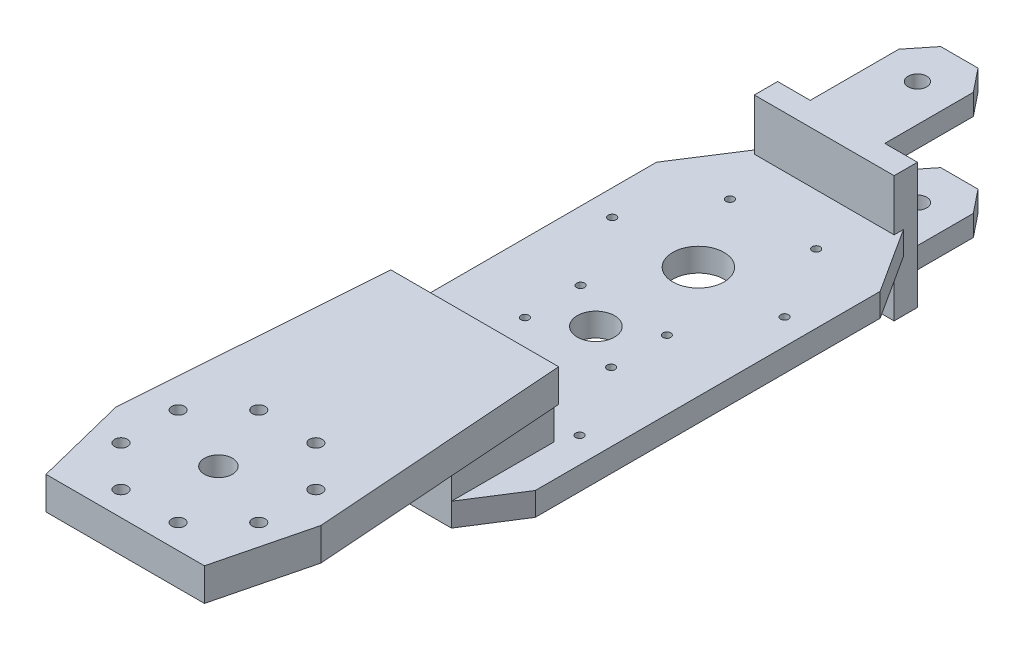
SolidWorks part; units mm, degrees
ref_plane "Front Plane" through (0, 0, 0) normal (0, 0, 1) x (1, 0, 0)
ref_plane "Top Plane" through (0, 0, 0) normal (0, 1, 0) x (1, 0, 0)
ref_plane "Right Plane" through (0, 0, 0) normal (1, 0, 0) x (0, 0, -1)
ref_plane "PL_Knee_Plate_base" through (0, 20, 0) normal (0, 1, 0) x (1, 0, 0)
sketch "SK_Knee_Plate" plane through (0, 20, 0) normal (0, 1, 0) x (1, 0, 0)
  line L0 (-34, -40) -> (34, -40)
  line L1 (34, -40) -> (44, 0)
  line L2 (44, 0) -> (36, 110)
  line L3 (36, 110) -> (-36, 110)
  line L4 (-36, 110) -> (-44, 0)
  line L5 (-44, 0) -> (-34, -40)
  circle A0 centre (29.5641, 12.2459) radius 2.75
  circle A1 centre (12.2459, 29.5641) radius 2.75
  circle A2 centre (-12.2459, 29.5641) radius 2.75
  circle A3 centre (-29.5641, 12.2459) radius 2.75
  circle A4 centre (-29.5641, -12.2459) radius 2.75
  circle A5 centre (-12.2459, -29.5641) radius 2.75
  circle A6 centre (12.2459, -29.5641) radius 2.75
  circle A7 centre (29.5641, -12.2459) radius 2.75
  circle A8 centre (0, 0) radius 6
  dimension "D11_SK_Knee_Plate" = 5.5
  dimension "D14_SK_Knee_Plate" = 5.5
  dimension "D17_SK_Knee_Plate" = 5.5
  dimension "D20_SK_Knee_Plate" = 5.5
  dimension "D23_SK_Knee_Plate" = 5.5
  dimension "D26_SK_Knee_Plate" = 5.5
  dimension "D29_SK_Knee_Plate" = 5.5
  dimension "D32_SK_Knee_Plate" = 5.5
  dimension "D35_SK_Knee_Plate" = 12
  dimension "P1" = 34
  dimension "P2" = 40
  dimension "P3" = 34
  dimension "P4" = 40
  dimension "P5" = 44
  dimension "P6" = 36
  dimension "P7" = 110
  dimension "P8" = 36
  dimension "P9" = 110
  dimension "P10" = 44
  dimension "P12" = 29.5641
  dimension "P13" = 12.2459
  dimension "P15" = 12.2459
  dimension "P16" = 29.5641
  dimension "P18" = 12.2459
  dimension "P19" = 29.5641
  dimension "P21" = 29.5641
  dimension "P22" = 12.2459
  dimension "P24" = 29.5641
  dimension "P25" = 12.2459
  dimension "P27" = 12.2459
  dimension "P28" = 29.5641
  dimension "P30" = 12.2459
  dimension "P31" = 29.5641
  dimension "P33" = 29.5641
  dimension "P34" = 12.2459
extrude "Knee_Plate" add sketch "SK_Knee_Plate" along normal blind 14
ref_plane "PL_Knee_Pilot_Recess_base" through (0, 20, 0) normal (0, 1, 0) x (1, 0, 0)
sketch "SK_Knee_Pilot_Recess" plane through (0, 20, 0) normal (0, 1, 0) x (1, 0, 0)
  circle A0 centre (0, 0) radius 25.15
  dimension "D1_SK_Knee_Pilot_Recess" = 50.3
extrude "Knee_Pilot_Recess" cut sketch "SK_Knee_Pilot_Recess" along normal blind 2.2
ref_plane "PL_Joggle_base" through (0, 0, -110) normal (0, 0, 1) x (1, 0, 0)
sketch "SK_Joggle" plane through (0, 0, -110) normal (0, 0, 1) x (1, 0, 0)
  line L0 (-34, 34) -> (34, 34)
  line L1 (34, 34) -> (34, -5)
  line L2 (34, -5) -> (-34, -5)
  line L3 (-34, -5) -> (-34, 34)
  dimension "P1" = 34
  dimension "P2" = 34
  dimension "P3" = 34
  dimension "P4" = 34
  dimension "P5" = 34
  dimension "P6" = 5
  dimension "P7" = 34
  dimension "P8" = 5
extrude "Joggle" add sketch "SK_Joggle" along normal blind 44
ref_plane "PL_Web_base" through (0, -5, 0) normal (0, 1, 0) x (1, 0, 0)
sketch "SK_Web" plane through (0, -5, 0) normal (0, 1, 0) x (1, 0, 0)
  line L0 (-34, 66) -> (34, 66)
  line L1 (34, 66) -> (48, 88)
  line L2 (48, 88) -> (48, 236)
  line L3 (48, 236) -> (30, 264)
  line L4 (30, 264) -> (-30, 264)
  line L5 (-30, 264) -> (-48, 236)
  line L6 (-48, 236) -> (-48, 88)
  line L7 (-48, 88) -> (-34, 66)
  circle A0 centre (37, 118) radius 1.7
  circle A1 centre (18.5, 150.0429) radius 1.7
  circle A2 centre (-18.5, 150.0429) radius 1.7
  circle A3 centre (-37, 118) radius 1.7
  circle A4 centre (-18.5, 85.9571) radius 1.7
  circle A5 centre (18.5, 85.9571) radius 1.7
  circle A6 centre (37, 206) radius 1.7
  circle A7 centre (18.5, 238.0429) radius 1.7
  circle A8 centre (-18.5, 238.0429) radius 1.7
  circle A9 centre (-37, 206) radius 1.7
  circle A10 centre (-18.5, 173.9571) radius 1.7
  circle A11 centre (18.5, 173.9571) radius 1.7
  circle A12 centre (0, 118) radius 11
  circle A13 centre (0, 206) radius 11
  circle A14 centre (0, 162) radius 8
  dimension "D17_SK_Web" = 3.4
  dimension "D20_SK_Web" = 3.4
  dimension "D23_SK_Web" = 3.4
  dimension "D26_SK_Web" = 3.4
  dimension "D29_SK_Web" = 3.4
  dimension "D32_SK_Web" = 3.4
  dimension "D35_SK_Web" = 3.4
  dimension "D38_SK_Web" = 3.4
  dimension "D41_SK_Web" = 3.4
  dimension "D44_SK_Web" = 3.4
  dimension "D47_SK_Web" = 3.4
  dimension "D50_SK_Web" = 3.4
  dimension "D53_SK_Web" = 22
  dimension "D55_SK_Web" = 22
  dimension "D57_SK_Web" = 16
  dimension "P1" = 34
  dimension "P2" = 66
  dimension "P3" = 34
  dimension "P4" = 66
  dimension "P5" = 48
  dimension "P6" = 88
  dimension "P7" = 48
  dimension "P8" = 236
  dimension "P9" = 30
  dimension "P10" = 264
  dimension "P11" = 30
  dimension "P12" = 264
  dimension "P13" = 48
  dimension "P14" = 236
  dimension "P15" = 48
  dimension "P16" = 88
  dimension "P18" = 37
  dimension "P19" = 118
  dimension "P21" = 18.5
  dimension "P22" = 150.0429
  dimension "P24" = 18.5
  dimension "P25" = 150.0429
  dimension "P27" = 37
  dimension "P28" = 118
  dimension "P30" = 18.5
  dimension "P31" = 85.9571
  dimension "P33" = 18.5
  dimension "P34" = 85.9571
  dimension "P36" = 37
  dimension "P37" = 206
  dimension "P39" = 18.5
  dimension "P40" = 238.0429
  dimension "P42" = 18.5
  dimension "P43" = 238.0429
  dimension "P45" = 37
  dimension "P46" = 206
  dimension "P48" = 18.5
  dimension "P49" = 173.9571
  dimension "P51" = 18.5
  dimension "P52" = 173.9571
  dimension "P54" = 118
  dimension "P56" = 206
  dimension "P58" = 162
extrude "Web" add sketch "SK_Web" along normal blind 10
ref_plane "PL_Fork_Bar_base" through (0, 0, -270) normal (0, 0, 1) x (1, 0, 0)
sketch "SK_Fork_Bar" plane through (0, 0, -270) normal (0, 0, 1) x (1, 0, 0)
  line L0 (-30, 27) -> (30, 27)
  line L1 (30, 27) -> (30, -27)
  line L2 (30, -27) -> (-30, -27)
  line L3 (-30, -27) -> (-30, 27)
  dimension "P1" = 30
  dimension "P2" = 27
  dimension "P3" = 30
  dimension "P4" = 27
  dimension "P5" = 30
  dimension "P6" = 27
  dimension "P7" = 30
  dimension "P8" = 27
extrude "Fork_Bar" add sketch "SK_Fork_Bar" along normal blind 10
ref_plane "PL_Tine_Lat_base" through (0, -27, 0) normal (0, 1, 0) x (1, 0, 0)
sketch "SK_Tine_Lat" plane through (0, -27, 0) normal (0, 1, 0) x (1, 0, 0)
  line L0 (-16, 260) -> (16, 260)
  line L1 (16, 260) -> (16, 308)
  line L2 (16, 308) -> (8, 318)
  line L3 (8, 318) -> (-8, 318)
  line L4 (-8, 318) -> (-16, 308)
  line L5 (-16, 308) -> (-16, 260)
  circle A0 centre (0, 300) radius 4
  dimension "D13_SK_Tine_Lat" = 8
  dimension "P1" = 16
  dimension "P2" = 260
  dimension "P3" = 16
  dimension "P4" = 260
  dimension "P5" = 16
  dimension "P6" = 308
  dimension "P7" = 8
  dimension "P8" = 318
  dimension "P9" = 8
  dimension "P10" = 318
  dimension "P11" = 16
  dimension "P12" = 308
  dimension "P14" = 300
extrude "Tine_Lat" add sketch "SK_Tine_Lat" along normal blind 9
ref_plane "PL_Tine_Med_base" through (0, 18, 0) normal (0, 1, 0) x (1, 0, 0)
sketch "SK_Tine_Med" plane through (0, 18, 0) normal (0, 1, 0) x (1, 0, 0)
  line L0 (-16, 260) -> (16, 260)
  line L1 (16, 260) -> (16, 308)
  line L2 (16, 308) -> (8, 318)
  line L3 (8, 318) -> (-8, 318)
  line L4 (-8, 318) -> (-16, 308)
  line L5 (-16, 308) -> (-16, 260)
  circle A0 centre (0, 300) radius 4
  dimension "D13_SK_Tine_Med" = 8
  dimension "P1" = 16
  dimension "P2" = 260
  dimension "P3" = 16
  dimension "P4" = 260
  dimension "P5" = 16
  dimension "P6" = 308
  dimension "P7" = 8
  dimension "P8" = 318
  dimension "P9" = 8
  dimension "P10" = 318
  dimension "P11" = 16
  dimension "P12" = 308
  dimension "P14" = 300
extrude "Tine_Med" add sketch "SK_Tine_Med" along normal blind 9
ref_plane "PL_AnkleZ" through (0, 0, -300) normal (0, 0, 1) x (1, 0, 0)
ref_axis "AX_AnklePitch" through (0, 37.05, -300) along (0, -1, 0)
ref_axis "AX_KneeY" through (0, 37.05, 0) along (0, -1, 0)
ref_plane "PL_KneeRef" through (0, 0, 0) normal (-0.9239, 0, 0.3827) x (0, -1, 0)
equation "\"Shin_length\" = 300"
equation "\"AnkleA_z\" = -118"
equation "\"AnkleB_z\" = -206"
